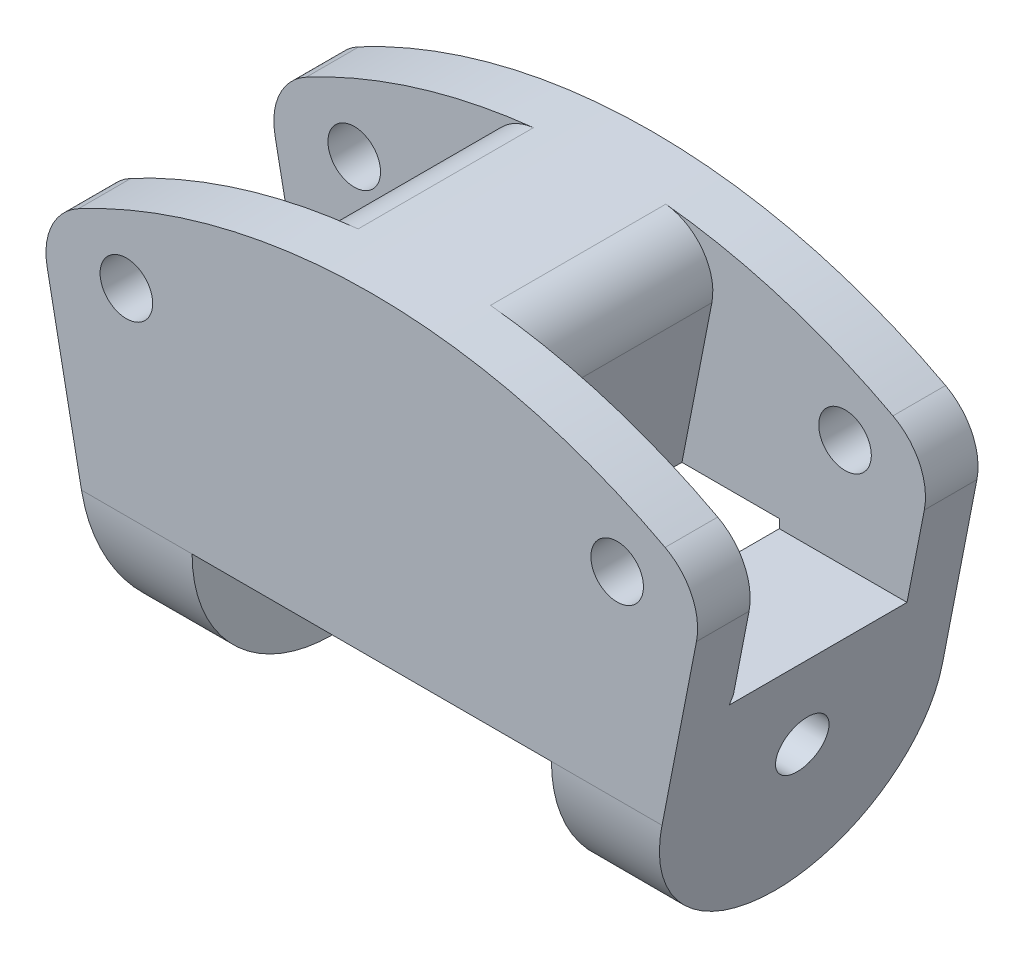
SolidWorks part; units mm, degrees
material "ABS"
ref_plane "Plan de face" through (0, 0, 0) normal (0, 0, 1) x (1, 0, 0)
ref_plane "Plan de dessus" through (0, 0, 0) normal (0, 1, 0) x (1, 0, 0)
ref_plane "Plan de droite" through (0, 0, 0) normal (1, 0, 0) x (0, 0, -1)
sketch "Esquisse1" plane through (0, 0, 0) normal (0, 0, 1) x (1, 0, 0)
  line L0 (15, 0) -> (-15, 0)
  line L1 (-15, 0) -> (-18.5236, 18.0583)
  line L2 (0, 0) -> (0, 90.7803) construction
  line L3 (15, 0) -> (18.5236, 18.0583)
  line L4 (-22.0061, 8) -> (9.675, 8) construction
  arc A0 (16.7351, 21.817) -> (-16.7351, 21.817) centre (0, -9.5682) ccw
  arc A1 (-16.7351, 21.817) -> (-18.5236, 18.0583) centre (-15.0884, 18.7286) ccw
  circle A2 centre (-14, 19.25) radius 1.5
  arc A3 (18.5236, 18.0583) -> (16.7351, 21.817) centre (15.0884, 18.7286) ccw
  circle A4 centre (14, 19.25) radius 1.5
  point P10 (-19, 16.8)
  point P17 (-19, 20.5)
  point P23 (19, 20.5)
  dimension "D5" = 3.5
  dimension "D6" = 3
  dimension "D1" = 30
  dimension "D2" = 38
  dimension "D3" = 19
  dimension "D4" = 20.5
  dimension "D7" = 28
  dimension "D8" = 8
  dimension "D9" = 11.25
extrude "Boss.-Extru.1" add sketch "Esquisse1" along normal mid plane 16
fillet "Congé1" radius 8 2 edges at (0, 0, -8) (0, 0, 8)
sketch "Esquisse2" plane through (0, 0, 0) normal (0, 0, 1) x (1, 0, 0)
  line L0 (15, 0) -> (-15, 0) construction
  line L1 (10.25, -0.9374) -> (-10.25, -0.9374)
  line L2 (10.25, -0.9374) -> (10.25, 8)
  line L3 (10.25, 8) -> (-10.25, 8)
  line L4 (-10.25, -0.9374) -> (-10.25, 8)
  dimension "D1" = 20.5
  dimension "D2" = 10.25
  dimension "D3" = 8
extrude "Enlèv. mat.-Extru.1" cut sketch "Esquisse2" against normal mid plane 20
ref_axis "Axe1" through (10.25, 8, 0) along (1, 0, 0)
sketch "Esquisse3" plane through (0, 0, 0) normal (0, 0, 1) x (1, 0, 0)
  line L0 (7, 25.3044) -> (4.5991, 13)
  line L1 (0, 0) -> (0, 33.6784) construction
  line L2 (16.561, 8) -> (18.5236, 18.0583) construction
  line L3 (17.5366, 13) -> (18.5236, 18.0583)
  line L4 (17.5366, 13) -> (4.5991, 13)
  line L5 (10.25, 8) -> (16.561, 8) construction
  line L6 (-17.5366, 13) -> (-18.5236, 18.0583)
  line L7 (-17.5366, 13) -> (-4.5991, 13)
  line L8 (-7, 25.3044) -> (-4.5991, 13)
  arc A0 (16.7351, 21.817) -> (-16.7351, 21.817) centre (0, -9.5682) ccw construction
  arc A1 (16.7351, 21.817) -> (7, 25.3044) centre (0, -9.5682) ccw
  arc A2 (18.5236, 18.0583) -> (16.7351, 21.817) centre (15.0884, 18.7286) ccw construction
  arc A3 (18.5236, 18.0583) -> (16.7351, 21.817) centre (15.0884, 18.7286) ccw
  arc A4 (-18.5236, 18.0583) -> (-16.7351, 21.817) centre (-15.0884, 18.7286) cw
  arc A5 (-16.7351, 21.817) -> (-7, 25.3044) centre (0, -9.5682) cw
  dimension "D1" = 5
  dimension "D2" = 7
extrude "Enlèv. mat.-Extru.2" cut sketch "Esquisse3" against normal mid plane 10
sketch "Esquisse4" plane through (0, 13, 0) normal (0, 1, 0) x (1, 0, 0)
  line L0 (4.5991, 5) -> (4.5991, -5) construction
  line L1 (4.5991, 5) -> (4.5991, -5)
  line L2 (4.5991, -5) -> (17.5366, -5) construction
  line L3 (4.5991, -5) -> (10.25, -5)
  line L4 (4.5991, 5) -> (17.5366, 5) construction
  line L5 (4.5991, 5) -> (10.25, 5)
  line L6 (10.25, 8) -> (10.25, -8) construction
  line L7 (10.25, 5) -> (10.25, -5)
  line L8 (-17.5366, -5) -> (-4.5991, -5) construction
  line L9 (-4.5991, 5) -> (-4.5991, -5) construction
  line L10 (-17.5366, 5) -> (-4.5991, 5) construction
  line L11 (-10.25, 8) -> (-10.25, -8) construction
  line L12 (-10.25, -5) -> (-4.5991, -5)
  line L13 (-4.5991, 5) -> (-4.5991, -5)
  line L14 (-10.25, 5) -> (-4.5991, 5)
  line L15 (-10.25, 5) -> (-10.25, -5)
extrude "Enlèv. mat.-Extru.3" cut sketch "Esquisse4" against normal up to surface (5 mm away) up to face at (0, 8, 0)
sketch "Esquisse6" plane through (10.25, 0, 0) normal (-1, 0, 0) x (0, 0, 1)
  circle A0 centre (0, 8) radius 1.5
  dimension "D1" = 3
extrude "Enlèv. mat.-Extru.4" cut sketch "Esquisse6" against normal through all and the other way through all
sketch "Esquisse7" plane through (0, 0, -8) normal (0, 0, -1) x (-1, 0, 0)
  line L0 (-10.25, 8) -> (10.25, 8) construction
  line L1 (-10.25, 8) -> (10.25, 8)
  line L2 (-10.25, 0) -> (-10.25, 8) construction
  line L3 (-10.25, 8) -> (-10.25, 13.5)
  line L4 (10.25, 8) -> (10.25, 0) construction
  line L5 (10.25, 13.5) -> (10.25, 8)
  line L6 (-10.25, 13.5) -> (10.25, 13.5)
  arc A0 (16.7351, 21.817) -> (-16.7351, 21.817) centre (0, -9.5682) ccw construction
  point P6 (0, 26)
  dimension "D1" = 12.5
extrude "Enlèv. mat.-Extru.5" cut sketch "Esquisse7" against normal up to surface (13 mm away) up to face at (15.5, 19.25, 5)
chamfer "Chanfrein1" distance 1.5 distance2 5.5 1 edges at (0, 8, 5) first distance on face at (0, 8, 6.5)
fillet "Congé2" radius 3 2 edges at (-7, 25.3044, 0) (7, 25.3044, 0)
